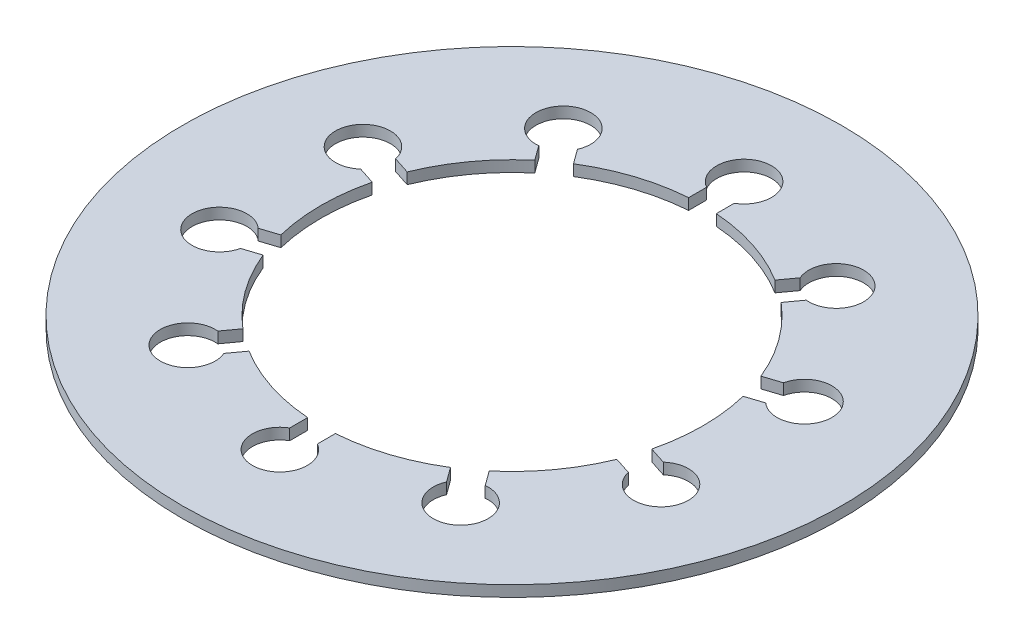
SolidWorks part; units mm, degrees
material "Alum Plate"
ref_plane "Front Plane" through (0, 0, 0) normal (0, 0, 1) x (1, 0, 0)
ref_plane "Top Plane" through (0, 0, 0) normal (0, 1, 0) x (1, 0, 0)
ref_plane "Right Plane" through (0, 0, 0) normal (1, 0, 0) x (0, 0, -1)
other "Bounding Box"
ref_plane "Default Plane" through (-8.9266, -12.7485, 0) normal (-0.1736, 0.9848, 0) x (0.9848, 0.1736, 0)
sketch "Sketch1" plane through (0, 0, 0) normal (0, 1, 0) x (1, 0, 0)
  circle A0 centre (0, 0) radius 17.4625 construction
  circle A1 centre (0, 0) radius 17.5006
  circle A2 centre (0, 0) radius 21.2725 construction
  circle A3 centre (0, 0) radius 30.2006
  dimension "D1" = 34.925
  dimension "D2" = 35.0012
  dimension "D3" = 3.81
  dimension "D4" = 12.7
extrude "Boss-Extrude1" add sketch "Sketch1" along normal blind 1.016
sketch "Sketch2" plane through (0, 1.016, 0) normal (0, 1, 0) x (1, 0, 0)
  line L0 (0, 17.4625) -> (0, 21.2725) construction
  line L2 (-1.27, 17.4545) -> (1.27, 17.4545)
  line L3 (-1.27, 17.4545) -> (-1.27, 19.1022)
  line L5 (1.27, 17.4545) -> (1.27, 19.1022)
  circle A0 centre (0, 0) radius 17.5006 construction
  arc A1 (1.27, 19.1022) -> (-1.27, 19.1022) centre (0, 21.2725) ccw
  circle A2 centre (0, 0) radius 17.4625 construction
  point P5 (0, 16.559)
  point P10 (0, 0)
  dimension "D1" = 5.0292
  dimension "D2" = 3.81
  dimension "D3" = 2.54
extrude "Cut-Extrude1" cut sketch "Sketch2" against normal through all
pattern_circular "CirPattern1" count 10 over 360 about axis through (0, 1.016, 0) along (0, -1, 0) of "Cut-Extrude1" reverse direction yes
